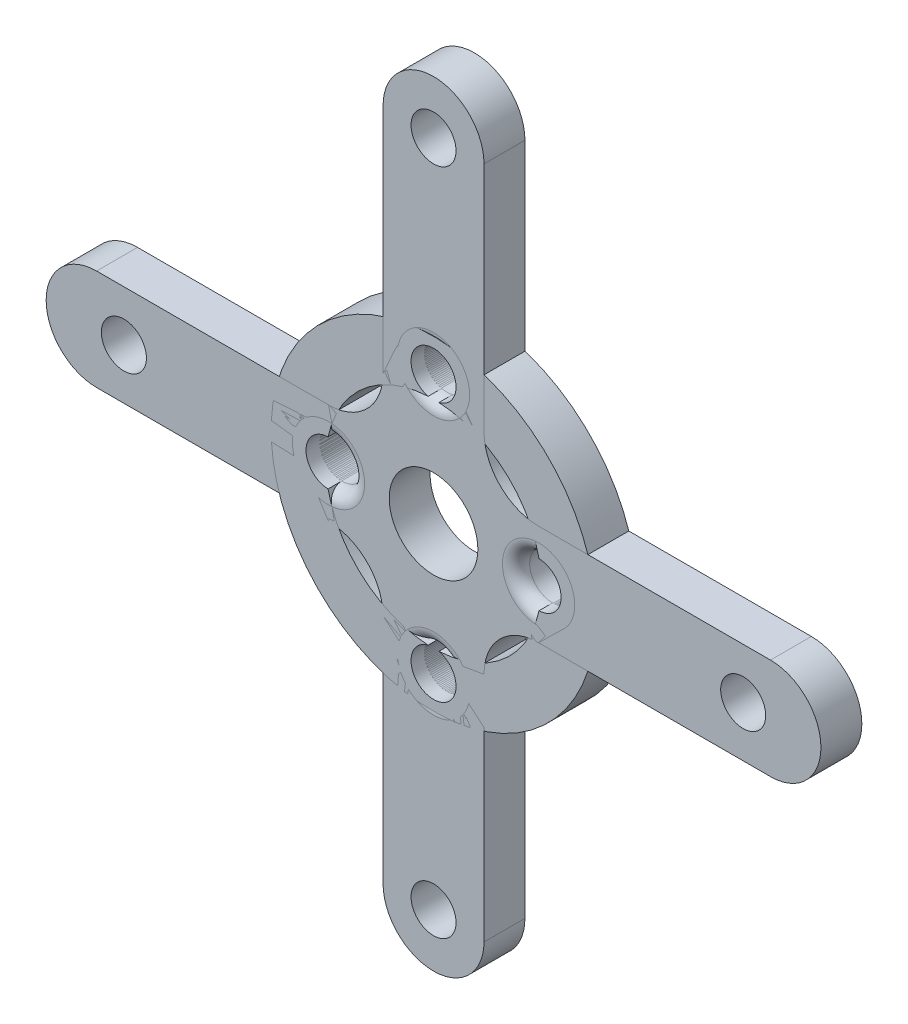
SolidWorks part; units mm, degrees
ref_plane "Alzado" through (0, 0, 0) normal (0, 0, 1) x (1, 0, 0)
ref_plane "Planta" through (0, 0, 0) normal (0, 1, 0) x (1, 0, 0)
ref_plane "Vista lateral" through (0, 0, 0) normal (1, 0, 0) x (0, 0, -1)
sketch "Croquis1" plane through (0, 0, 0) normal (0, 0, 1) x (1, 0, 0)
  line L9 (-7.7, 3.7) -> (-24.7, 3.7)
  line L10 (-7.7, -3.7) -> (-24.7, -3.7)
  line L12 (-3.7, -7.7) -> (-3.7, -24.7)
  line L13 (3.7, -7.7) -> (3.7, -24.7)
  line L15 (7.7, -3.7) -> (24.7, -3.7)
  line L16 (7.7, 3.7) -> (24.7, 3.7)
  line L18 (-3.7, 7.7) -> (-3.7, 24.7)
  line L19 (3.7, 7.7) -> (3.7, 24.7)
  circle A0 centre (0, 0) radius 5
  circle A5 centre (-17.7, 0) radius 1.65
  circle A6 centre (17.7, 0) radius 1.65
  circle A7 centre (0, -17.7) radius 1.65
  circle A8 centre (0, 17.7) radius 1.65
  arc A9 (-7.7, 3.7) -> (-3.7, 7.7) centre (-7.7, 7.7) ccw
  arc A10 (3.7, 7.7) -> (7.7, 3.7) centre (7.7, 7.7) ccw
  arc A11 (-3.7, -7.7) -> (-7.7, -3.7) centre (-7.7, -7.7) ccw
  arc A12 (7.7, -3.7) -> (3.7, -7.7) centre (7.7, -7.7) ccw
  arc A13 (3.7, 24.7) -> (-3.7, 24.7) centre (0, 24.7) ccw
  arc A14 (-3.7, -24.7) -> (3.7, -24.7) centre (0, -24.7) ccw
  arc A16 (-24.7, 3.7) -> (-24.7, -3.7) centre (-24.7, 0) ccw
  arc A17 (24.7, -3.7) -> (24.7, 3.7) centre (24.7, 0) ccw
  circle A18 centre (-17.7, 0) radius 1.65
  circle A19 centre (0, 0) radius 7.9076
  circle A20 centre (0, 0) radius 11.9076
  dimension "D1" = 10
  dimension "D2" = 3.3
  dimension "D5" = 3.3
  dimension "D6" = 3.3
  dimension "D9" = 3.3
  dimension "D18" = 4
  dimension "D26" = 17
  dimension "D27" = 17
  dimension "D28" = 17
  dimension "D29" = 17
extrude "Saliente-Extruir2" add sketch "Croquis1" along normal blind 3 contours L15 A17 L16 A10 L19 A13 L18 A9 L9 A16 L10 A11 L12 A14 L13 A12
sketch "Croquis3" plane through (0, 0, 3) normal (0, 0, 1) x (1, 0, 0)
  line L0 (-7.7, 0) -> (-22.7, 0) construction
  line L1 (0, 9.5) -> (0, 24.5) construction
  line L2 (7.7, 0) -> (22.7, 0) construction
  line L3 (0, -9.5) -> (0, -24.5) construction
  circle A1 centre (0, 0) radius 3.25
  circle A2 centre (-7.7, 0) radius 1.65
  circle A3 centre (-22.7, 0) radius 1.65
  circle A4 centre (0, -9.5) radius 1.65
  circle A5 centre (7.7, 0) radius 1.65
  circle A6 centre (0, 9.5) radius 1.65
  circle A7 centre (0, 24.5) radius 1.65
  circle A8 centre (22.7, 0) radius 1.65
  circle A9 centre (0, -24.5) radius 1.65
  dimension "D1" = 6.5
  dimension "D3" = 3.3
  dimension "D5" = 3.3
  dimension "D6" = 3.3
  dimension "D7" = 3.3
  dimension "D8" = 3.3
  dimension "D15" = 3.3
  dimension "D16" = 3.3
  dimension "D17" = 3.3
  dimension "D2" = 7.7
  dimension "D4" = 15
  dimension "D9" = 9.5
  dimension "D10" = 7.7
  dimension "D11" = 9.5
  dimension "D12" = 15
  dimension "D13" = 15
  dimension "D14" = 15
extrude "Cortar-Extruir1" cut sketch "Croquis3" against normal blind 10 and the other way blind 10 from offset 0
extrude "Saliente-Extruir3" add sketch "Croquis1<15>" along normal blind 3 separate body contours A19 | A20
sketch "Croquis1<15>" plane through (0, 0, 0) normal (0, 0, 1) x (1, 0, 0) same geometry as "Croquis1"
extrude "Cortar-Extruir2" cut sketch "Croquis3<2>" against normal blind 3
sketch "Croquis3<2>" plane through (0, 0, 3) normal (0, 0, 1) x (1, 0, 0) same geometry as "Croquis3"
fillet "Redondeo2" radius 1 1 edges at (-6.05, 0, 3) type face fillet first side face at (-6.05, 0, 3) second side face at (-6.05, 0, 3)
fillet "Redondeo3" radius 1 1 edges at (1.65, 9.5, 3) type face fillet first side face at (-5.05, 0, 3) second side face at (1.65, 9.5, 3)
fillet "Redondeo4" radius 1 1 edges at (9.35, 0, 3) type face fillet first side face at (2.65, 9.5, 3) second side face at (9.35, 0, 3)
fillet "Redondeo5" radius 1 1 edges at (1.65, -9.5, 3) type face fillet first side face at (10.35, 0, 3) second side face at (1.65, -9.5, 3)
